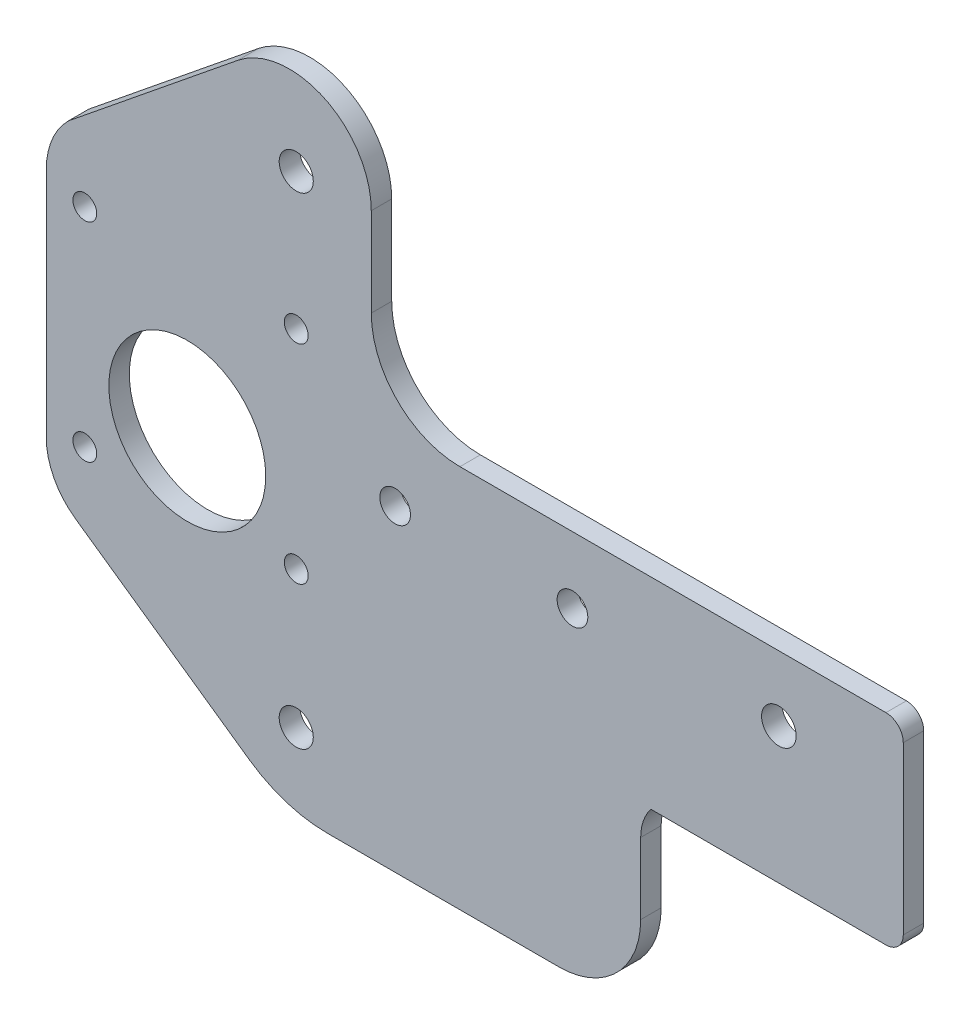
SolidWorks part; units mm, degrees
ref_plane "Front Plane" through (0, 0, 0) normal (0, 0, 1) x (1, 0, 0)
ref_plane "Top Plane" through (0, 0, 0) normal (0, 1, 0) x (1, 0, 0)
ref_plane "Right Plane" through (0, 0, 0) normal (1, 0, 0) x (0, 0, -1)
sketch "Sketch1" plane through (0, 0, 0) normal (0, 0, 1) x (1, 0, 0)
  line L0 (0, 0) -> (0, -29.5)
  line L1 (0, -29.5) -> (-37, -29.5)
  line L2 (0, 0) -> (-65, 0)
  line L3 (-78, 13) -> (-78, 26)
  line L4 (-97.5518, 35.3258) -> (-122.4205, 15.1875)
  line L5 (-125.65, 7.4017) -> (-125.65, -26.5983)
  line L6 (-89, 5.5) -> (-89, -25) construction
  line L7 (-120, 5.5) -> (-89, 5.5) construction
  line L8 (-121.3858, -34.7898) -> (-95.8858, -52.6451)
  line L9 (-84.4142, -56.2621) -> (-50.5, -56.2621)
  line L10 (-38.5, -44.2621) -> (-38.5, -33.8301)
  line L11 (-104.5, -9.75) -> (-104.5, 5.5) construction
  line L12 (-104.5, -9.75) -> (-89, -9.75) construction
  arc A0 (-78, 13) -> (-65, 0) centre (-65, 13) ccw
  arc A1 (-78, 26) -> (-97.5518, 35.3258) centre (-90, 26) ccw
  arc A2 (-122.4205, 15.1875) -> (-125.65, 7.4017) centre (-114.65, 7.4017) ccw
  arc A3 (-125.65, -26.5983) -> (-121.3858, -34.7898) centre (-115.65, -26.5983) ccw
  arc A4 (-95.8858, -52.6451) -> (-84.4142, -56.2621) centre (-84.4142, -36.2621) ccw
  arc A5 (-50.5, -56.2621) -> (-38.5, -44.2621) centre (-50.5, -44.2621) ccw
  arc A6 (-37, -29.5) -> (-38.5, -33.8301) centre (-31.5, -33.8301) ccw
  circle A7 centre (-18.237, -9.552) radius 2.54
  circle A8 centre (-48.5, -9.75) radius 2.25
  circle A9 centre (-74.5, -9.75) radius 2.25
  circle A10 centre (-89, 5.5) radius 1.75
  circle A11 centre (-89, 25.5) radius 2.5
  circle A12 centre (-89, -25) radius 1.75
  circle A13 centre (-89, -45.112) radius 2.5
  circle A14 centre (-104.975, -15.4503) radius 11.5
  circle A15 centre (-120, 5.5) radius 1.75
  circle A16 centre (-120, -25) radius 1.75
  dimension "D4" = 24
  dimension "D5" = 26
  dimension "D12" = 20
  dimension "D16" = 14
  dimension "D17" = 24
  dimension "D19" = 5.08
  dimension "D20" = 4.5
  dimension "D21" = 4.5
  dimension "D22" = 31
  dimension "D23" = 5
  dimension "D25" = 5
  dimension "D11" = 3.5
  dimension "D1" = 65
  dimension "D2" = 29.5
  dimension "D3" = 37
  dimension "D6" = 13
  dimension "D7" = 32
  dimension "D8" = 51
  dimension "D10" = 34
  dimension "D14" = 125
  dimension "D15" = 25.5
  dimension "D18" = 1.5
  dimension "D29" = 70.763
  dimension "D30" = 9.75
  dimension "D31" = 9.75
  dimension "D34" = 25.5
  dimension "D37" = 70.612
  dimension "D39" = 35.56
  dimension "D40" = 48.5
  dimension "D41" = 74.5
  dimension "D42" = 89
extrude "Boss-Extrude1" add sketch "Sketch1" along normal blind 3
fillet "Fillet2" radius 2.54 2 edges at (0, 0, 1.5) (0, -29.5, 1.5)
